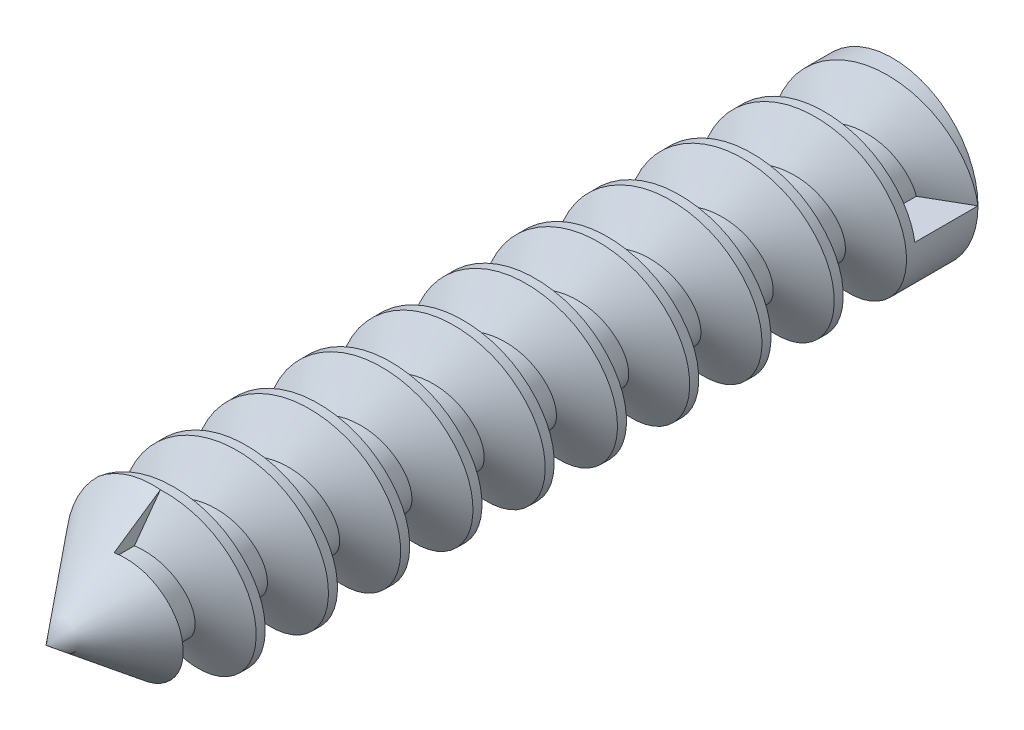
SolidWorks part; units mm, degrees
ref_plane "前视基准面" through (0, 0, 0) normal (0, 0, 1) x (1, 0, 0)
ref_plane "上视基准面" through (0, 0, 0) normal (0, 1, 0) x (1, 0, 0)
ref_plane "右视基准面" through (0, 0, 0) normal (1, 0, 0) x (0, 0, -1)
sketch "草图1" plane through (0, 0, 0) normal (0, 0, 1) x (1, 0, 0)
  circle A0 centre (0, 0) radius 1.5
extrude "凸台-拉伸1" add sketch "草图1" along normal blind 13
sketch "草图2" plane through (0, 0, 0) normal (0, 1, 0) x (1, 0, 0)
  line L0 (0, -13) -> (0, -14.8815)
  line L1 (-1.5, -13) -> (1.5, -13) construction
  line L2 (0, -14.8815) -> (-1.5, -13)
  line L3 (-1.5, -13) -> (0, -13)
  point P5 (0, -14.8815)
revolve "旋转1" add sketch "草图2" angle 360 about L0
thread "螺纹线1" pitch 1.27 method cut profile "螺纹线轮廓1" start angle 0, offset 0, length 0, pitch 1.27, diameter 3
ref_plane "基准面1" through (1.5, 0, 0) normal (0, -1, 0) x (1, 0, 0)
sketch "螺纹线轮廓1" plane through (1.5, 0, 0) normal (0, -1, 0) x (1, 0, 0)
  line L0 (0, 0) -> (0, 1.27) construction
  line L11 (0, 0) -> (0, 1.1112)
  line L12 (0, 1.1112) -> (-0.6874, 0.7144)
  line L13 (-0.6874, 0.7144) -> (-0.6874, 0.3969)
  line L15 (-0.6874, 0.3969) -> (0, 0)
  line L17 (-0.6874, 0.5556) -> (0, 0.5556) construction
  point P2 (0, 0)
  dimension "Pitch" = 1.27
  dimension "Profile_Angle" = 60
  dimension "Profile_Land" = 0.3175
  dimension "Profile_Height" = 0.6874
